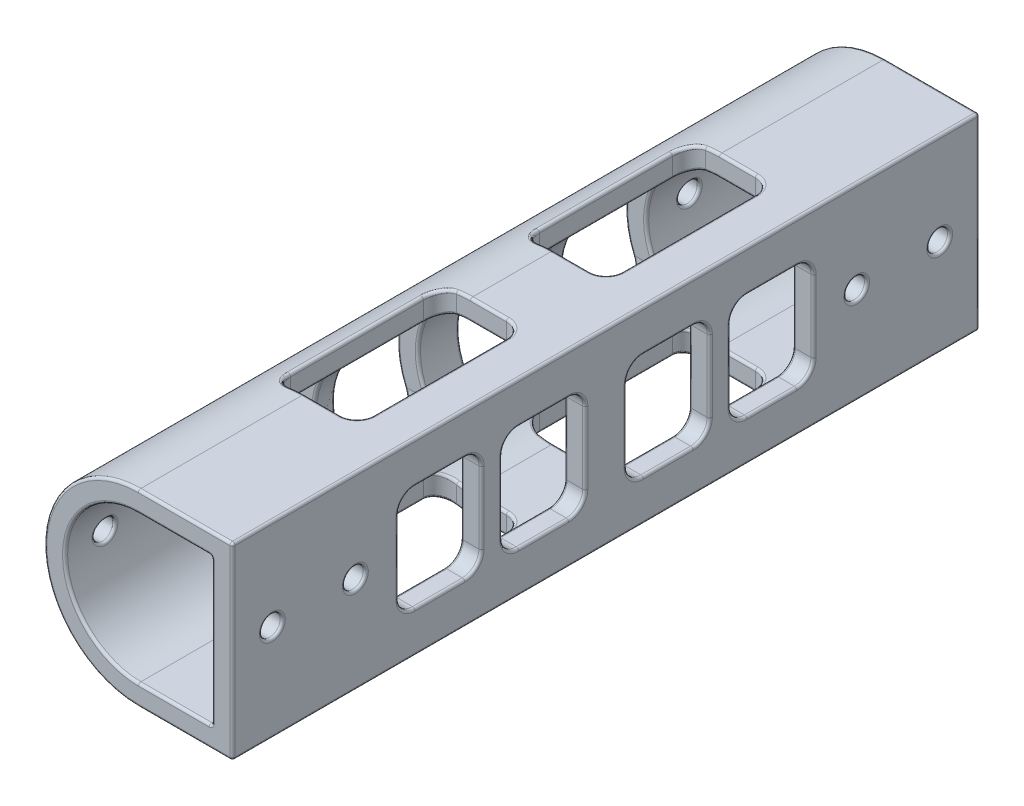
SolidWorks part; units mm, degrees
ref_plane "Front Plane" through (0, 0, 0) normal (0, 0, 1) x (1, 0, 0)
ref_plane "Top Plane" through (0, 0, 0) normal (0, 1, 0) x (1, 0, 0)
ref_plane "Right Plane" through (0, 0, 0) normal (1, 0, 0) x (0, 0, -1)
sketch "Sketch1" plane through (0, 0, 0) normal (0, 0, 1) x (1, 0, 0)
  line L1 (0, 13.9792) -> (14.3954, 13.9792)
  line L2 (0, 13.9792) -> (0, -14.8117)
  line L3 (0, -14.8117) -> (14.3955, -14.8117)
  line L4 (14.3954, 13.9792) -> (14.3955, -14.8117)
  line L5 (11.2204, -11.6367) -> (0, -11.6367)
  line L6 (11.2204, -11.6367) -> (11.2204, 10.8042)
  line L7 (11.2204, 10.8042) -> (0, 10.8042)
  line L8 (0, -11.6367) -> (0, 10.8042)
  arc A0 (0, -11.6367) -> (0, 10.8042) centre (0, -0.4163) cw
  arc A1 (0, 13.9792) -> (0, -14.8117) centre (0, -0.4163) ccw
  dimension "D1" = 28.7909
  dimension "D2" = 14.3954
  dimension "D3" = 3.175
  dimension "D4" = 3.175
  dimension "D5" = 3.175
extrude "Boss-Extrude1" add sketch "Sketch1" along normal blind 114.3 contours L2 A1 A0 | L7 L6 L5 L2 L3 L4 L1 region at (7.1977, 13.6573, 0) region at (-0.3219, 12.3917, 0)
sketch "Sketch3" plane through (0, 0, 0) normal (1, 0, 0) x (0, 0, -1)
  line L6 (0, 13.9792) -> (0, -14.8117) construction
  line L11 (-114.3, -11.6367) -> (0, -11.6367) construction
  line L12 (-86.36, -8.4617) -> (-78.74, -8.4617)
  line L13 (-88.9, -5.9217) -> (-88.9, 5.0892)
  line L14 (-86.36, 7.6292) -> (-78.74, 7.6292)
  line L15 (-76.2, -5.9217) -> (-76.2, 5.0892)
  line L17 (-114.3, 10.8042) -> (0, 10.8042) construction
  line L18 (-114.3, -11.6367) -> (-114.3, 10.8042) construction
  line L22 (-70.485, -8.4617) -> (-62.865, -8.4617)
  line L23 (-73.025, -5.9217) -> (-73.025, 5.0892)
  line L24 (-70.485, 7.6292) -> (-62.865, 7.6292)
  line L25 (-60.325, -5.9217) -> (-60.325, 5.0892)
  line L26 (-35.56, -8.4617) -> (-27.94, -8.4617)
  line L27 (-38.1, -5.9217) -> (-38.1, 5.0892)
  line L28 (-35.56, 7.6292) -> (-27.94, 7.6292)
  line L29 (-25.4, -5.9217) -> (-25.4, 5.0892)
  line L31 (-51.435, -8.4617) -> (-43.815, -8.4617)
  line L32 (-53.975, -5.9217) -> (-53.975, 5.0892)
  line L33 (-51.435, 7.6292) -> (-43.815, 7.6292)
  line L34 (-41.275, -5.9217) -> (-41.275, 5.0892)
  arc A3 (-76.2, 5.0892) -> (-78.74, 7.6292) centre (-78.74, 5.0892) ccw
  arc A4 (-78.74, -8.4617) -> (-76.2, -5.9217) centre (-78.74, -5.9217) ccw
  arc A5 (-88.9, -5.9217) -> (-86.36, -8.4617) centre (-86.36, -5.9217) ccw
  arc A6 (-88.9, 5.0892) -> (-86.36, 7.6292) centre (-86.36, 5.0892) cw
  arc A7 (-38.1, 5.0892) -> (-35.56, 7.6292) centre (-35.56, 5.0892) cw
  arc A8 (-25.4, 5.0892) -> (-27.94, 7.6292) centre (-27.94, 5.0892) ccw
  arc A9 (-27.94, -8.4617) -> (-25.4, -5.9217) centre (-27.94, -5.9217) ccw
  arc A10 (-60.325, -5.9217) -> (-62.865, -8.4617) centre (-62.865, -5.9217) cw
  arc A11 (-60.325, 5.0892) -> (-62.865, 7.6292) centre (-62.865, 5.0892) ccw
  arc A12 (-73.025, 5.0892) -> (-70.485, 7.6292) centre (-70.485, 5.0892) cw
  arc A13 (-73.025, -5.9217) -> (-70.485, -8.4617) centre (-70.485, -5.9217) ccw
  arc A14 (-38.1, -5.9217) -> (-35.56, -8.4617) centre (-35.56, -5.9217) ccw
  arc A15 (-41.275, 5.0892) -> (-43.815, 7.6292) centre (-43.815, 5.0892) ccw
  arc A16 (-53.975, 5.0892) -> (-51.435, 7.6292) centre (-51.435, 5.0892) cw
  arc A17 (-51.435, -8.4617) -> (-53.975, -5.9217) centre (-51.435, -5.9217) cw
  arc A18 (-43.815, -8.4617) -> (-41.275, -5.9217) centre (-43.815, -5.9217) ccw
  point P28 (-76.2, -0.4163)
  point P49 (-47.625, 7.6292)
  dimension "D2" = 3.175
  dimension "D4" = 12.7
  dimension "D5" = 2.54
  dimension "D14" = 2.54
  dimension "D15" = 2.54
  dimension "D20" = 2.54
  dimension "D1" = 3.175
  dimension "D3" = 25.4
  dimension "D6" = 25.4
  dimension "D7" = 12.7
  dimension "D8" = 3.175
  dimension "D9" = 12.7
  dimension "D10" = 3.175
  dimension "D11" = 3.175
  dimension "D12" = 3.175
  dimension "D13" = 3.175
  dimension "D16" = 12.7
  dimension "D17" = 6.35
  dimension "D18" = 3.175
  dimension "D19" = 3.175
extrude "Cut-Extrude1" cut sketch "Sketch3" against normal blind 25.4 and the other way blind 25.4
sketch "Sketch6" plane through (0, 0, 0) normal (0, 1, 0) x (1, 0, 0)
  line L5 (0, -114.3) -> (14.3954, -114.3) construction
  line L6 (-2.1145, -25.4) -> (5.5054, -25.4)
  line L11 (-4.6546, -27.94) -> (-4.6545, -48.26)
  line L12 (-2.1145, -50.8) -> (5.5054, -50.8)
  line L13 (8.0454, -27.94) -> (8.0455, -48.26)
  line L14 (5.5054, -88.9) -> (-2.1145, -88.9)
  line L15 (8.0454, -86.36) -> (8.0454, -66.04)
  line L16 (5.5054, -63.5) -> (-2.1145, -63.5)
  line L17 (-4.6546, -86.36) -> (-4.6546, -66.04)
  line L18 (11.2204, -114.3) -> (11.2204, 0) construction
  line L19 (0, 0) -> (14.3954, 0) construction
  arc A0 (-2.1145, -88.9) -> (-4.6546, -86.36) centre (-2.1146, -86.36) cw
  arc A1 (8.0454, -86.36) -> (5.5054, -88.9) centre (5.5054, -86.36) cw
  arc A2 (-2.1145, -63.5) -> (-4.6546, -66.04) centre (-2.1146, -66.04) ccw
  arc A3 (8.0454, -66.04) -> (5.5054, -63.5) centre (5.5054, -66.04) ccw
  arc A4 (-2.1145, -50.8) -> (-4.6545, -48.26) centre (-2.1145, -48.26) cw
  arc A5 (5.5054, -50.8) -> (8.0455, -48.26) centre (5.5055, -48.26) ccw
  arc A6 (-2.1145, -25.4) -> (-4.6546, -27.94) centre (-2.1146, -27.94) ccw
  arc A7 (5.5054, -25.4) -> (8.0454, -27.94) centre (5.5054, -27.94) cw
  point P21 (8.0454, -88.9)
  point P26 (8.0454, -63.5)
  dimension "D7" = 2.54
  dimension "D1" = 25.4
  dimension "D2" = 25.4
  dimension "D3" = 3.175
  dimension "D4" = 12.7
  dimension "D5" = 25.4
  dimension "D6" = 25.4
extrude "Cut-Extrude2" cut sketch "Sketch6" against normal blind 25.4 and the other way blind 25.4
sketch "Sketch7" plane through (0, 0, 0) normal (1, 0, 0) x (0, 0, -1)
  line L0 (-114.3, 0) -> (0, 0) construction
  line L2 (-114.3, 13.9792) -> (-114.3, -14.8117) construction
  line L3 (-57.15, -21.0207) -> (-57.15, 21.0207)
  line L6 (0, 13.9792) -> (0, -14.8117) construction
  circle A0 centre (-108.204, 0) radius 1.5875
  circle A1 centre (-95.504, 0) radius 1.5875
  circle A2 centre (-18.796, 0) radius 1.5875
  circle A3 centre (-6.096, 0) radius 1.5875
  point P3 (-111.5194, 0)
  point P12 (-57.15, 0)
  point P13 (-57.15, 0)
  dimension "D2" = 3.175
  dimension "D1" = 6.096
  dimension "D3" = 12.7
  dimension "D4" = 6.096
extrude "Cut-Extrude3" cut sketch "Sketch7" against normal blind 25.4 and the other way blind 25.4 contours A3 | A2 | A1 | A0
fillet "Fillet3" radius 0.3969 242 edges at (2.7527, -14.8117, 25.4) (-1.0602, -14.7726, 25.4) (-3.9296, -14.265, 26.1632) (-4.6546, -14.0384, 38.1) (2.7527, -14.8117, 63.5) (-1.0602, -14.7726, 63.5) (-3.9296, -14.265, 64.2632) (-4.6546, -14.0384, 76.2) (-7.8211, 7.6292, 31.75) (-8.9167, 6.3948, 25.7612) (-11.2204, -0.4163, 25.4) (-7.8211, 7.6292, 66.675) (-8.9167, 6.3948, 60.6862) (-11.2204, -0.4163, 60.325) (-7.8211, 7.6292, 47.625) (-8.9167, 6.3948, 41.6362) (-11.2204, -0.4163, 41.275) (-7.8211, 7.6292, 82.55) (-8.9167, 6.3948, 76.5612) (-11.2204, -0.4163, 76.2) (5.6102, 10.8042, 114.3) (7.1977, -14.8117, 114.3) (14.3954, -0.4163, 25.4) (14.3954, 6.8852, 26.1439) (14.3954, 7.6292, 31.75) (14.3954, -0.4163, 60.325) (14.3954, 6.8852, 61.0689) (14.3954, 7.6292, 66.675) (14.3954, -0.4163, 41.275) (14.3954, 6.8852, 42.0189) (14.3954, 7.6292, 47.625) (14.3954, -0.4163, 76.2) (14.3954, 6.8852, 76.9439) (14.3954, 7.6292, 82.55) (2.7527, 10.8042, 25.4) (-1.062, 10.7538, 25.4) (-3.9799, 10.0746, 26.216) (-4.6546, 9.7932, 38.1) (-4.6546, -10.6257, 38.1) (2.7527, 10.8042, 63.5) (-1.062, 10.7538, 63.5) (-3.9799, 10.0746, 64.316) (-4.6546, 9.7932, 76.2) (-4.6546, -10.6257, 76.2) (14.3954, 1.5875, 108.204) (11.2204, 0, 109.7915) (-11.1946, 0.3452, 106.6545) (-14.3953, -0.3557, 106.6569) (14.3954, 1.5875, 95.504) (11.2204, 0, 97.0915) (-11.1946, 0.3452, 93.9545) (-14.3953, -0.3557, 93.9569) (14.3954, 1.5875, 18.796) (11.2204, 0, 20.3835) (-11.2203, -0.3496, 17.2475) (-14.3749, 0.353, 17.2482) (14.3954, 1.5875, 6.096) (11.2204, 0, 7.6835) (-11.2203, -0.3496, 4.5475) (-14.3749, 0.353, 4.5482) (-1.062, -11.5863, 25.4) (2.7527, 13.9792, 25.4) (-1.0602, 13.9401, 25.4) (7.3015, 10.8042, 26.1439) (7.3015, -14.8117, 26.1439) (7.3015, 13.9792, 26.1439) (8.0455, 10.8042, 38.1) (8.0455, -14.8117, 38.1) (8.0455, 13.9792, 38.1) (7.3015, 10.8042, 50.0561) (7.3015, -14.8117, 50.0561) (7.3015, 13.9792, 50.0561) (-1.062, -11.5863, 50.8) (2.7527, 10.8042, 50.8) (-1.062, 10.7538, 50.8) (2.7527, -14.8117, 50.8) (-1.0602, -14.7726, 50.8) (2.7527, 13.9792, 50.8) (-1.0602, 13.9401, 50.8) (-1.062, -11.5863, 63.5) (2.7527, 13.9792, 63.5) (-1.0602, 13.9401, 63.5) (7.3015, 10.8042, 64.2439) (7.3015, -14.8117, 64.2439) (7.3015, 13.9792, 64.2439) (8.0454, 10.8042, 76.2) (8.0454, -14.8117, 76.2) (8.0454, 13.9792, 76.2) (7.3015, 10.8042, 88.1561) (7.3015, -14.8117, 88.1561) (7.3015, 13.9792, 88.1561) (-1.062, -11.5863, 88.9) (2.7527, 10.8042, 88.9) (-1.062, 10.7538, 88.9) (2.7527, -14.8117, 88.9) (-1.0602, -14.7726, 88.9) (2.7527, 13.9792, 88.9) (-1.0602, 13.9401, 88.9) (-4.6546, 13.2059, 38.1) (-3.7235, 13.4893, 25.9746) (-3.7235, -14.3218, 50.2254) (-3.9296, 13.4325, 50.0368) (-4.6546, 13.2059, 76.2) (-3.7235, 13.4893, 64.0746) (-3.7235, -14.3218, 88.3254) (-3.9296, 13.4325, 88.1368) (11.2204, 7.6292, 31.75) (-11.9373, 7.6292, 31.75) (11.2204, 6.8852, 26.1439) (-12.3169, 7.0351, 26.3075) (11.2204, -0.4163, 25.4) (-14.3954, -0.4163, 25.4) (11.2204, -7.7178, 26.1439) (-8.1547, -8.1234, 26.6734) (-12.4616, -7.6231, 26.054) (11.2204, -8.4617, 31.75) (-7.8211, -8.4617, 31.75) (-11.9373, -8.4617, 31.75) (11.2204, -7.7178, 37.3561) (-8.4657, -7.7804, 37.2911) (-12.1897, -8.0739, 36.9089) (11.2204, -0.4163, 38.1) (-11.2204, -0.4163, 38.1) (-14.3954, -0.4163, 38.1) (11.2204, 6.8852, 37.3561) (-10.584, 3.309, 33.7482) (-13.9576, 3.107, 33.9717) (11.2204, -8.4617, 66.675) (-7.8211, -8.4617, 66.675) (-11.9373, -8.4617, 66.675) (11.2204, -7.7178, 72.2811) (-8.4657, -7.7804, 72.2161) (-13.9064, -4.1365, 68.6782) (11.2204, -0.4163, 73.025) (-11.2204, -0.4163, 73.025) (-14.3954, -0.4163, 73.025) (11.2204, 6.8852, 72.2811) (-10.584, 3.309, 68.6732) (-12.4616, 6.7906, 72.371) (11.2204, 7.6292, 66.675) (-11.9373, 7.6292, 66.675) (11.2204, 6.8852, 61.0689) (-12.3169, 7.0351, 61.2325) (11.2204, -0.4163, 60.325) (-14.3954, -0.4163, 60.325) (11.2204, -7.7178, 61.0689) (-8.2858, -7.9822, 61.3797) (-12.6651, -7.259, 60.7055) (11.2204, -0.4163, 41.275) (-14.3954, -0.4163, 41.275) (11.2204, -7.7178, 42.0189) (-8.1547, -8.1234, 42.5484) (-12.4616, -7.6231, 41.929) (11.2204, -8.4617, 47.625) (-7.8211, -8.4617, 47.625) (-11.9373, -8.4617, 47.625) (11.2204, -7.7178, 53.2311) (-8.4657, -7.7804, 53.1661) (-13.9064, -4.1365, 49.6282) (11.2204, -0.4163, 53.975) (-11.2204, -0.4163, 53.975) (-14.3954, -0.4163, 53.975) (11.2204, 6.8852, 53.2311) (-10.584, 3.309, 49.6232) (-13.9576, 3.107, 49.8467) (11.2204, 7.6292, 47.625) (-11.9373, 7.6292, 47.625) (11.2204, 6.8852, 42.0189) (-12.3169, 7.0351, 42.1825) (11.2204, -0.4163, 76.2) (-14.3954, -0.4163, 76.2) (11.2204, -7.7178, 76.9439) (-8.2858, -7.9822, 77.2547) (-12.6651, -7.259, 76.5805) (11.2204, -8.4617, 82.55) (-7.8211, -8.4617, 82.55) (-11.9373, -8.4617, 82.55) (11.2204, -7.7178, 88.1561) (-10.6875, -3.8333, 84.9143) (-13.9064, -4.1365, 84.5532) (11.2204, -0.4163, 88.9) (-11.2204, -0.4163, 88.9) (-14.3954, -0.4163, 88.9) (11.2204, 6.8852, 88.1561) (-8.4, 7.0228, 88.0071) (-12.4616, 6.7906, 88.246) (11.2204, 7.6292, 82.55) (-11.9373, 7.6292, 82.55) (11.2204, 6.8852, 76.9439) (-12.3169, 7.0351, 77.1075) (-11.2204, -0.4163, 0) (5.6102, 10.8042, 0) (11.2204, -0.4163, 0) (5.6102, -11.6367, 0) (7.1977, 13.9792, 0) (-14.3954, -0.4163, 0) (7.1977, -14.8117, 0) (14.3954, -0.4163, 0) (-11.2204, -0.4163, 114.3) (11.2204, -0.4163, 114.3) (5.6102, -11.6367, 114.3) (7.1977, 13.9792, 114.3) (-14.3954, -0.4163, 114.3) (11.2204, -11.6367, 57.15) (11.2204, 10.8042, 57.15) (14.3954, 13.9792, 57.15) (14.3954, -7.7178, 26.1439) (14.3955, -8.4617, 31.75) (14.3955, -7.7178, 37.3561) (14.3954, -0.4163, 38.1) (14.3954, 6.8852, 37.3561) (14.3955, -8.4617, 66.675) (14.3955, -7.7178, 72.2811) (14.3954, -0.4163, 73.025) (14.3954, 6.8852, 72.2811) (14.3954, -7.7178, 61.0689) (14.3954, -7.7178, 42.0189) (14.3955, -8.4617, 47.625) (14.3955, -7.7178, 53.2311) (14.3954, -0.4163, 53.975) (14.3954, 6.8852, 53.2311) (14.3954, -7.7178, 76.9439) (14.3955, -8.4617, 82.55) (14.3955, -7.7178, 88.1561) (14.3954, -0.4163, 88.9) (14.3954, 6.8852, 88.1561) (2.7527, -11.6367, 25.4) (7.3015, -11.6367, 26.1439) (8.0455, -11.6367, 38.1) (7.3015, -11.6367, 50.0561) (2.7527, -11.6367, 50.8) (2.7527, -11.6367, 63.5) (7.3015, -11.6367, 64.2439) (8.0454, -11.6367, 76.2) (7.3015, -11.6367, 88.1561) (2.7527, -11.6367, 88.9) (-3.7003, 10.1765, 50.2442) (-3.7003, -11.009, 25.9558) (-3.9799, -10.9072, 49.984) (-3.7003, 10.1765, 88.3442) (-3.7003, -11.009, 64.0558) (-3.9799, -10.9072, 88.084)
fillet "Fillet4" radius 0.3969 5 edges at (14.2792, 13.863, 114.1838) (14.2792, -14.6955, 0.1162) (14.3955, -14.8117, 57.15) (14.3955, -14.6955, 114.1838) (14.3954, -0.4163, 114.3)
